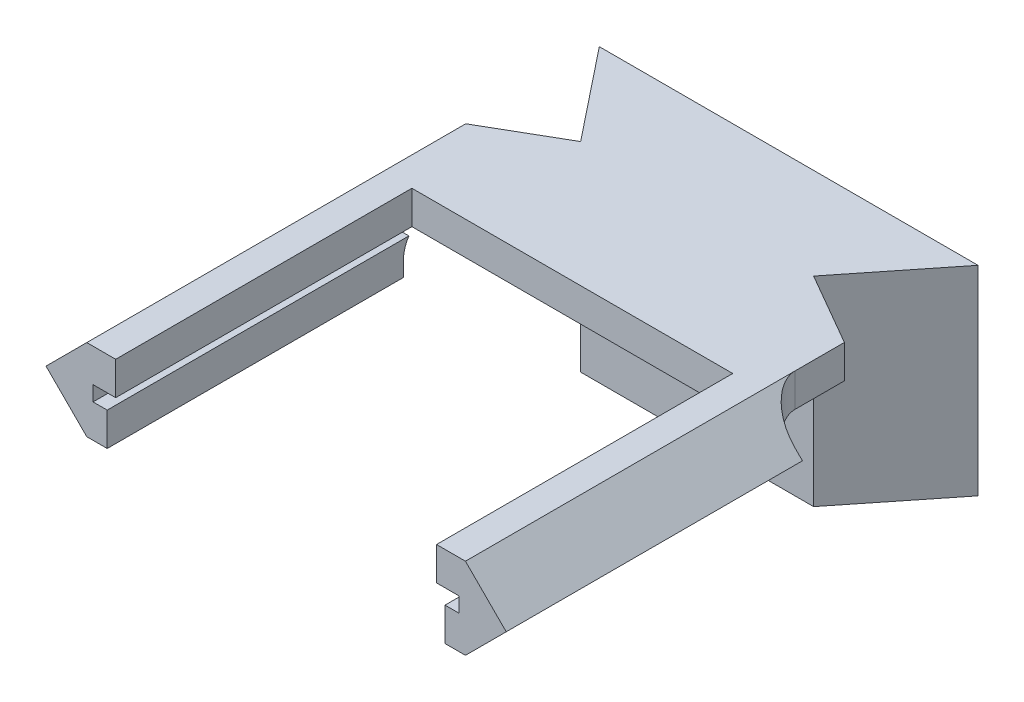
SolidWorks part; units mm, degrees
ref_plane "Front Plane" through (0, 0, 0) normal (0, 0, 1) x (1, 0, 0)
ref_plane "Top Plane" through (0, 0, 0) normal (0, 1, 0) x (1, 0, 0)
ref_plane "Right Plane" through (0, 0, 0) normal (1, 0, 0) x (0, 0, -1)
sketch "Sketch1" plane through (0, 0, 0) normal (0, 0, 1) x (1, 0, 0)
  line L0 (0.8255, 1.143) -> (0, 1.143)
  line L1 (0, 0) -> (0.8255, 0) construction
  line L2 (0, 0) -> (0, 1.143) construction
  line L3 (0, 1.143) -> (0.8255, 1.143) construction
  line L4 (0.8255, 0) -> (0.8255, 1.143) construction
  line L5 (0.4127, 1.143) -> (0.4128, 0) construction
  line L6 (0, 0.5715) -> (0.8255, 0.5715) construction
  line L7 (0.8255, 0) -> (0, 0)
  line L8 (0, 0) -> (-0.5715, 0.5715) construction
  line L9 (-0.5715, 0.5715) -> (0, 1.143) construction
  line L10 (25.9715, 0) -> (26.797, 0)
  line L11 (0.8255, 1.143) -> (25.9715, 1.143)
  line L12 (0.8255, 1.143) -> (0.8255, 0) construction
  line L13 (0.8255, 0) -> (25.9715, 0)
  line L14 (25.9715, 1.143) -> (25.9715, 0) construction
  line L15 (13.3985, 0) -> (13.3985, 1.143) construction
  line L16 (0.8255, 0.5715) -> (25.9715, 0.5715) construction
  line L17 (26.797, 0) -> (27.3685, 0.5715) construction
  line L18 (25.9715, 1.143) -> (26.797, 1.143)
  line L19 (27.3685, 0.5715) -> (26.797, 1.143) construction
  line L20 (-4.1636, 0.5715) -> (-1.0521, 3.683)
  line L21 (0.8255, 3.683) -> (-1.0521, 3.683)
  line L22 (0.8255, 3.683) -> (25.9715, 3.683)
  line L23 (25.9715, 3.683) -> (27.8491, 3.683)
  line L24 (30.9606, 0.5715) -> (27.8491, 3.683)
  line L25 (27.8491, -2.54) -> (30.9606, 0.5715)
  line L26 (25.9715, -2.54) -> (27.8491, -2.54)
  line L27 (0.8255, -2.54) -> (25.9715, -2.54)
  line L28 (0.8255, -2.54) -> (-1.0521, -2.54)
  line L29 (-1.0521, -2.54) -> (-4.1636, 0.5715)
  line L30 (0, 1.143) -> (-0.5715, 1.143)
  line L31 (-0.5715, 1.143) -> (-0.5715, 0)
  line L32 (-0.5715, 0) -> (0, 0)
  line L33 (26.797, 1.143) -> (27.3685, 1.143)
  line L34 (27.3685, 1.143) -> (27.3685, 0)
  line L35 (27.3685, 0) -> (26.797, 0)
  point P287 (13.3985, 0.5715)
  point P500 (0.4127, 0.5715)
  dimension "D1" = 1.143
  dimension "D2" = 0.8255
  dimension "D3" = 45
  dimension "D4" = 25.146
  dimension "D5" = 2.54
extrude "Boss-Extrude1" add sketch "Sketch1" along normal blind 22.606
sketch "Sketch2" plane through (0, 0, 22.606) normal (0, 0, 1) x (1, 0, 0)
  line L5 (13.3985, 0) -> (13.3985, -2.54) construction
  line L6 (-0.5715, 0) -> (27.3685, 0) construction
  line L7 (-1.0521, -2.54) -> (27.8491, -2.54) construction
  line L9 (0.508, 0) -> (26.289, 0)
  line L10 (0.508, 0) -> (0.508, -2.54)
  line L11 (0.508, -2.54) -> (26.289, -2.54)
  line L12 (26.289, 0) -> (26.289, -2.54)
  line L13 (13.3985, -2.54) -> (13.3985, 0) construction
  line L14 (0.508, -1.27) -> (26.289, -1.27) construction
  point P218 (13.3985, -1.27)
  dimension "D1" = 0.508
extrude "Cut-Extrude1" cut sketch "Sketch2" against normal blind 22.606
sketch "Sketch5" plane through (0, 0, 0) normal (0, 0, -1) x (-1, 0, 0)
  line L12 (-30.9606, 0.5715) -> (-27.3685, 0.5715)
  line L13 (-27.3685, 0.5715) -> (-27.3685, 1.143)
  line L14 (-27.3685, 1.143) -> (0.5715, 1.143)
  line L15 (0.5715, 1.143) -> (0.5715, 0.5715)
  line L16 (0.5715, 1.143) -> (0.5715, 0) construction
  line L17 (0.5715, 0.5715) -> (4.1636, 0.5715)
  line L18 (4.1636, 0.5715) -> (1.0521, 3.683)
  line L19 (1.0521, 3.683) -> (-27.8491, 3.683)
  line L20 (-27.8491, 3.683) -> (-30.9606, 0.5715)
extrude "Boss-Extrude2" add sketch "Sketch5" along normal blind 16.51
sketch "Sketch3" plane through (0, 3.683, 0) normal (0, 1, 0) x (1, 0, 0)
  line L0 (13.3985, 0) -> (13.3985, -22.606) construction
  line L1 (27.8491, 0) -> (-1.0521, 0) construction
  line L2 (27.8491, -22.606) -> (-1.0521, -22.606) construction
  line L3 (6.1023, -15.0622) -> (2.9845, -15.0622) construction
  line L4 (1.1557, 0) -> (25.6413, 0) construction
  line L5 (1.1557, 0) -> (1.1557, -22.606) construction
  line L6 (1.1557, -22.606) -> (25.6413, -22.606) construction
  line L7 (25.6413, 0) -> (25.6413, -22.606) construction
  line L8 (13.3985, -22.606) -> (13.3985, 0) construction
  line L9 (1.1557, -11.303) -> (25.6413, -11.303) construction
  line L10 (6.1023, 0) -> (20.6947, 0) construction
  line L11 (6.1023, 0) -> (6.1023, -15.0622) construction
  line L12 (6.1023, -15.0622) -> (20.6947, -15.0622) construction
  line L13 (20.6947, 0) -> (20.6947, -15.0622) construction
  line L14 (13.3985, -15.0622) -> (13.3985, 0) construction
  line L15 (6.1023, -7.5311) -> (20.6947, -7.5311) construction
  line L16 (2.9845, 0) -> (23.8125, 0) construction
  line L17 (2.9845, 0) -> (2.9845, -22.606) construction
  line L18 (2.9845, -22.606) -> (23.8125, -22.606) construction
  line L19 (23.8125, 0) -> (23.8125, -22.606) construction
  line L20 (13.3985, -22.606) -> (13.3985, 0) construction
  line L21 (2.9845, -11.303) -> (23.8125, -11.303) construction
  line L22 (2.9845, -15.0622) -> (2.9845, 0) construction
  line L23 (2.9845, 0) -> (1.1557, 0)
  line L24 (1.1557, 0) -> (1.1557, -22.606)
  line L25 (1.1557, -22.606) -> (25.6413, -22.606)
  line L26 (25.6413, -22.606) -> (25.6413, 0)
  line L27 (25.6413, 0) -> (23.8125, 0)
  line L28 (23.8125, 0) -> (23.8125, -15.0622) construction
  line L29 (23.8125, -15.0622) -> (20.6947, -15.0622) construction
  line L32 (6.1023, 0) -> (20.6947, 0)
  line L33 (2.9845, 0) -> (6.1023, 0)
  line L34 (20.6947, 0) -> (23.8125, 0)
  point P250 (13.3985, -11.303)
  point P383 (13.3985, -7.5311)
  point P386 (13.3985, -11.303)
  dimension "D1" = 24.4856
  dimension "D2" = 14.5923
  dimension "D3" = 15.0622
  dimension "D4" = 20.828
extrude "Cut-Extrude4" cut sketch "Sketch3" against normal up to vertex (2.54 mm away) up to point (27.3685, 1.143, 22.606)
sketch "Sketch6" plane through (0, 0, -16.51) normal (0, 0, -1) x (-1, 0, 0)
  line L2 (-27.8491, 3.683) -> (-30.9606, 0.5715)
  line L3 (-30.9606, 0.5715) -> (-27.3685, 0.5715)
  line L4 (-27.3685, 0.5715) -> (-27.3685, 1.143)
  line L5 (-27.3685, 1.143) -> (-27.8491, 1.143)
  line L6 (-27.8491, 1.143) -> (-27.8491, 3.683)
  line L8 (-13.3985, 3.683) -> (-13.3985, 1.143) construction
  line L9 (-0.8255, 3.683) -> (-25.9715, 3.683) construction
  line L11 (1.0521, 1.143) -> (1.0521, 3.683)
  line L12 (0.5715, 1.143) -> (1.0521, 1.143)
  line L13 (0.5715, 0.5715) -> (0.5715, 1.143)
  line L14 (4.1636, 0.5715) -> (0.5715, 0.5715)
  line L15 (1.0521, 3.683) -> (4.1636, 0.5715)
extrude "Cut-Extrude5" cut sketch "Sketch6" against normal up to surface (16.51 mm away) up to face at (27.6875, -0.6562, 0)
fillet "Fillet1" radius 2.54 4 edges at (-0.8118, 1.143, 0) (-1.0521, 2.413, 0) (27.6088, 1.143, 0) (27.8491, 2.413, 0)
sketch "Sketch7" plane through (0, 1.143, 0) normal (0, -1, 0) x (1, 0, 0)
  line L3 (27.8491, -16.51) -> (22.2885, -9.525)
  line L4 (-1.0521, -9.525) -> (27.8491, -9.525) construction
  line L5 (-1.0521, -2.54) -> (-1.0521, -16.51) construction
  line L6 (27.8491, -2.54) -> (27.8491, -16.51) construction
  line L7 (13.3985, 0) -> (13.3985, -12.7) construction
  line L8 (25.6413, 0) -> (1.1557, 0) construction
  line L9 (-1.0521, -16.51) -> (4.5085, -9.525)
  line L10 (4.5085, -9.525) -> (22.2885, -9.525) construction
  line L11 (-1.0521, -16.51) -> (27.8491, -16.51)
  line L14 (-1.0521, -2.54) -> (-1.0521, -16.51)
  line L15 (27.8491, -16.51) -> (27.8491, -2.54)
  line L16 (-1.0521, -16.51) -> (-1.0521, -9.525)
  line L17 (-1.0521, -9.525) -> (4.5085, -9.525) construction
  line L18 (27.8491, -16.51) -> (27.8491, -9.525)
  line L19 (27.8491, -9.525) -> (22.2885, -9.525) construction
  line L20 (4.5085, -9.525) -> (-1.0521, -6.3146)
  line L21 (22.2885, -9.525) -> (27.8491, -6.3146)
  dimension "D1" = 17.78
  dimension "D2" = 30
  dimension "D3" = 6.985
extrude "Cut-Extrude6" cut sketch "Sketch7" against normal up to surface (2.54 mm away)
sketch "Sketch8" plane through (0, 1.143, 0) normal (0, -1, 0) x (1, 0, 0)
  line L9 (-1.0521, -16.51) -> (27.8491, -16.51)
  line L12 (-1.0521, -16.51) -> (4.5085, -9.525)
  line L13 (4.5085, -9.525) -> (22.2885, -9.525)
  line L14 (22.2885, -9.525) -> (27.8491, -16.51)
extrude "Boss-Extrude3" add sketch "Sketch8" along normal blind 12.7
sketch "Sketch9" plane through (0, 0, -16.51) normal (0, 0, -1) x (-1, 0, 0)
  line L0 (-27.8491, -3.937) -> (1.0521, -3.937) construction
  line L7 (-13.3985, 3.683) -> (-13.3985, -11.557) construction
  line L8 (1.0521, 3.683) -> (-27.8491, 3.683) construction
  line L9 (1.0521, -11.557) -> (-27.8491, -11.557) construction
  line L10 (-27.8491, -11.557) -> (-27.8491, 3.683) construction
  line L11 (1.0521, 3.683) -> (1.0521, -11.557) construction
  circle A3 centre (-18.4785, -3.937) radius 2
  circle A4 centre (-8.3185, -3.937) radius 2
  dimension "D1" = 4
  dimension "D2" = 5.08
extrude "Cut-Extrude7" cut sketch "Sketch9" against normal up to surface (6.985 mm away) up to face at (13.3985, -5.207, -9.525)
